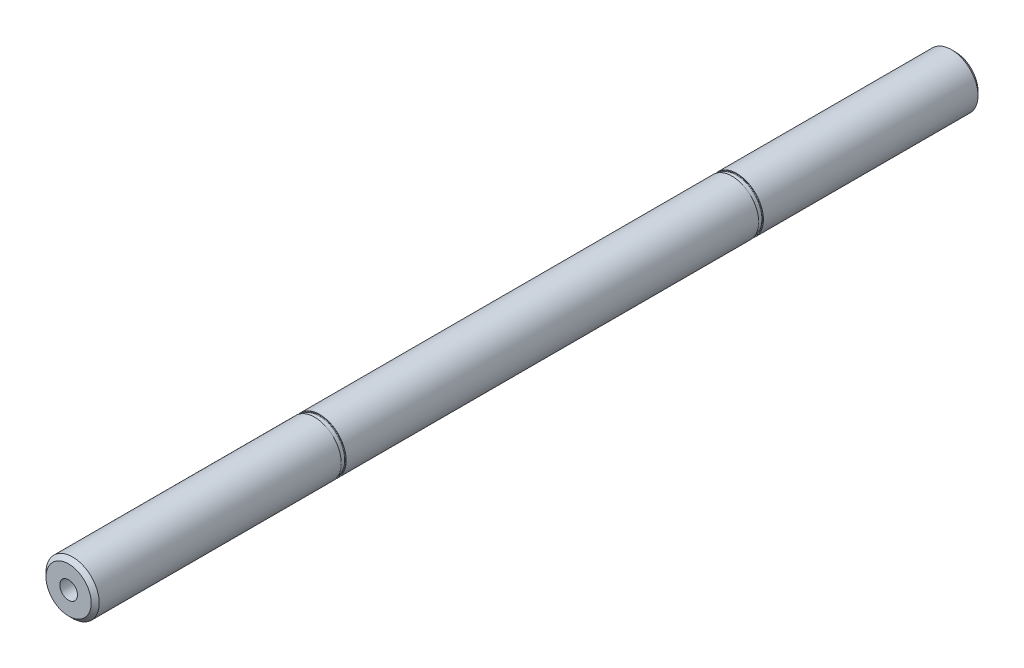
SolidWorks part; units mm, degrees
material "AISI 1045 Steel, cold drawn"
ref_plane "Front" through (0, 0, 0) normal (0, 0, 1) x (1, 0, 0)
ref_plane "Top" through (0, 0, 0) normal (0, 1, 0) x (1, 0, 0)
ref_plane "Right" through (0, 0, 0) normal (1, 0, 0) x (0, 0, -1)
sketch "Sketch1" plane through (0, 0, 0) normal (0, 0, 1) x (1, 0, 0)
  circle A0 centre (0, 0) radius 6
  dimension "OD" = 12
extrude "Extrude1" add sketch "Sketch1" along normal mid plane 200
chamfer "Chamfer1" distance 0.9 angle 45 2 edges at (6, 0, -100) (6, 0, 100)
sketch "Sketch2" plane through (0, 0, 0) normal (0, 0, 1) x (1, 0, 0)
  circle A0 centre (0, 0) radius 2
  dimension "ID" = 4
extrude "Extrude3" cut sketch "Sketch2" against normal through all and the other way through all
ref_plane "Plane1" through (0, 6, 0) normal (0, 1, 0) x (1, 0, 0)
ref_plane "Plane2" through (0, 0, 100) normal (-1, 0, 0) x (0, 1, 0)
sketch "Sketch5" plane through (0, 0, 100) normal (-1, 0, 0) x (0, 1, 0)
  line L0 (5.86, 55.5) -> (7.2, 55.5)
  line L1 (7.2, 55.5) -> (7.2, 56.6)
  line L2 (7.2, 56.6) -> (5.86, 56.6)
  line L3 (5.75, 56.49) -> (5.75, 55.61)
  line L4 (0, -50) -> (0, 50) construction
  arc A0 (5.75, 55.61) -> (5.86, 55.5) centre (5.86, 55.61) ccw
  arc A1 (5.75, 56.49) -> (5.86, 56.6) centre (5.86, 56.49) cw
  dimension "D1" = 0.11
  dimension "D2" = 0.11
  dimension "D3" = 55.5
revolve "Groove for DIN 471 - 12 x 1, Circlip for shafts - normal1" cut sketch "Sketch5"
ref_plane "Plane3" through (0, 0, 100) normal (-1, 0, 0) x (0, 1, 0)
sketch "Sketch7" plane through (0, 0, 100) normal (-1, 0, 0) x (0, 1, 0)
  line L0 (5.899, 149.6072) -> (7.1982, 150.1)
  line L1 (7.1982, 150.1) -> (7.2, 150.7)
  line L2 (7.2, 150.7) -> (5.86, 150.7)
  line L3 (5.75, 150.59) -> (5.75, 149.71)
  line L4 (0, -50) -> (0, 50) construction
  line L6 (-6, 56.6) -> (6, 56.6) construction
  arc A0 (5.75, 149.71) -> (5.899, 149.6072) centre (5.86, 149.71) ccw
  arc A1 (5.75, 150.59) -> (5.86, 150.7) centre (5.86, 150.59) cw
  dimension "D1" = 0.11
  dimension "D2" = 0.11
  dimension "D3" = 93.5
revolve "Groove for DIN 471 - 12 x 1, Circlip for shafts - normal2" cut sketch "Sketch7" angle 360 about L4 reverse direction yes
equation "\"D1@Chamfer1\" = \"OD@Sketch1\" * .075"
